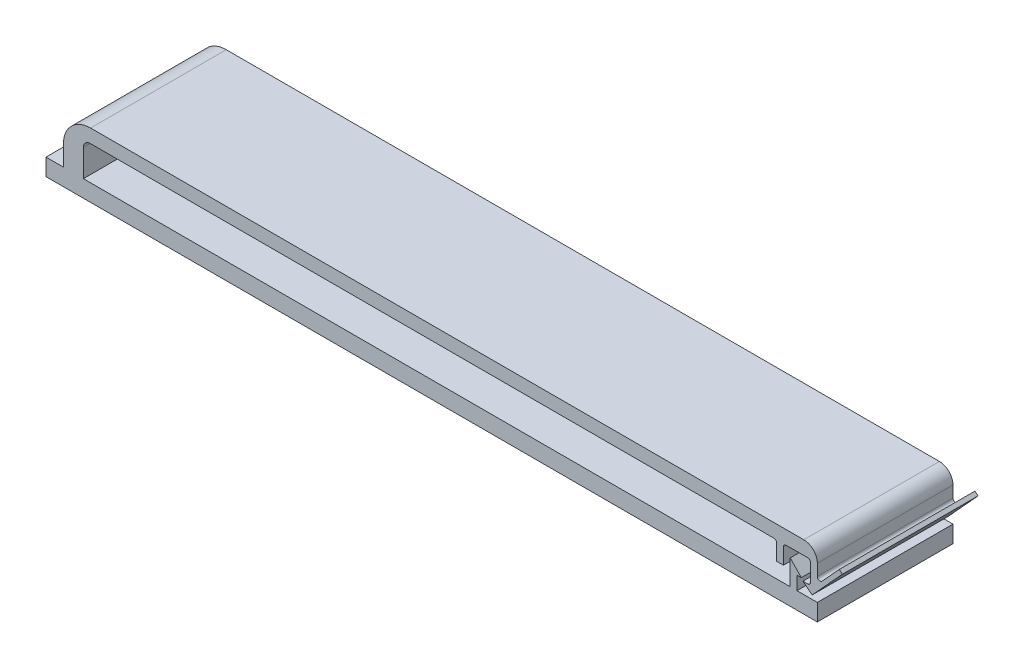
SolidWorks part; units mm, degrees
ref_plane "Front Plane" through (0, 0, 0) normal (0, 0, 1) x (1, 0, 0)
ref_plane "Top Plane" through (0, 0, 0) normal (0, 1, 0) x (1, 0, 0)
ref_plane "Right Plane" through (0, 0, 0) normal (1, 0, 0) x (0, 0, -1)
sketch "Sketch1" plane through (0, 0, 0) normal (0, 0, 1) x (1, 0, 0)
  line L0 (70.3072, 1.5875) -> (70.3072, 2.846)
  line L1 (0, 0) -> (72.2122, 0)
  line L2 (0, 0) -> (0, 1.5875)
  line L3 (0, 1.5875) -> (1.6355, 1.5875)
  line L4 (72.2122, 0) -> (72.2122, 1.5875)
  line L5 (70.3072, 2.846) -> (70.7132, 2.846)
  line L6 (70.7132, 2.846) -> (69.6722, 3.9305)
  line L7 (69.6722, 3.9305) -> (69.6722, 1.5875)
  line L8 (1.6355, 1.5875) -> (1.6355, 3.4925)
  line L9 (4.1755, 6.0325) -> (72.2122, 6.0325)
  line L10 (72.2122, 6.0325) -> (72.2122, 3.6986)
  line L11 (74.5538, 5.0406) -> (71.7331, 1.9558)
  line L13 (71.5772, 2.888) -> (71.5772, 4.5085)
  line L14 (71.3232, 4.7625) -> (69.2912, 4.7625)
  line L15 (3.5005, 4.1275) -> (3.5005, 1.5875)
  line L16 (3.5005, 1.5875) -> (69.6722, 1.5875)
  line L17 (70.3072, 1.5875) -> (72.2122, 1.5875)
  line L18 (68.4022, 4.5085) -> (68.4022, 3.0176)
  line L19 (68.4022, 3.0176) -> (69.0372, 3.0176)
  line L20 (69.0372, 4.5085) -> (69.0372, 3.0176)
  line L21 (68.1482, 4.7625) -> (4.1355, 4.7625)
  line L22 (71.3232, 2.634) -> (70.8586, 2.634)
  line L23 (74.5538, 5.0406) -> (74.2726, 5.2977)
  line L24 (74.2726, 5.2977) -> (72.6537, 3.5272)
  line L25 (70.8586, 2.634) -> (71.7331, 1.9558)
  arc A0 (1.6355, 3.4925) -> (4.1755, 6.0325) centre (4.1755, 3.4925) cw
  arc A1 (4.1355, 4.7625) -> (3.5005, 4.1275) centre (4.1355, 4.1275) ccw
  arc A2 (72.6537, 3.5272) -> (72.2122, 3.6986) centre (72.4662, 3.6986) cw
  arc A3 (71.5772, 4.5085) -> (71.3232, 4.7625) centre (71.3232, 4.5085) ccw
  arc A4 (69.2912, 4.7625) -> (69.0372, 4.5085) centre (69.2912, 4.5085) ccw
  arc A5 (68.1482, 4.7625) -> (68.4022, 4.5085) centre (68.1482, 4.5085) cw
  arc A6 (71.3232, 2.634) -> (71.5772, 2.888) centre (71.3232, 2.888) ccw
  point P27 (3.5005, 4.7625)
  point P39 (68.4022, 4.7625)
  dimension "D5" = 2.54
  dimension "D6" = 0.635
  dimension "D13" = 0.254
  dimension "D14" = 0.254
  dimension "D15" = 0.254
  dimension "D1" = 72.2122
  dimension "D2" = 1.5875
  dimension "D3" = 3.175
  dimension "D4" = 4.445
  dimension "D7" = 0.635
  dimension "D8" = 1.905
  dimension "D9" = 0.635
  dimension "D10" = 0.635
  dimension "D11" = 0.381
  dimension "D12" = 0.635
extrude "Extrude1" add sketch "Sketch1" against normal blind 12.7
fillet "Fillet1" radius 1.27 1 edges at (72.2122, 6.0325, -6.35)
sketch "Sketch2" plane through (0, 0, 0) normal (0, 0, 1) x (1, 0, 0)
  point P5 (36.1419, 3.1595)
ref_axis "Clip Axis" through (36.1419, 3.1595, 0) along (0, 0, -1)
ref_axis "Axis of Rotation" through (36.1419, 3.1595, 0) along (0, 1, 0)
